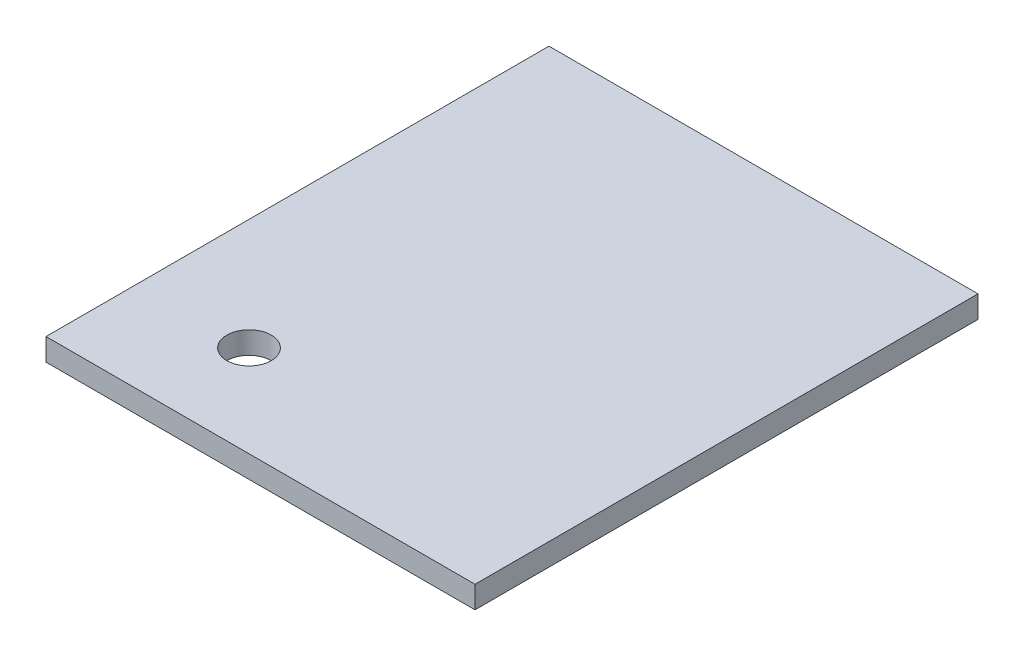
SolidWorks part; units mm, degrees
ref_plane "Front Plane" through (0, 0, 0) normal (0, 0, 1) x (1, 0, 0)
ref_plane "Top Plane" through (0, 0, 0) normal (0, 1, 0) x (1, 0, 0)
ref_plane "Right Plane" through (0, 0, 0) normal (1, 0, 0) x (0, 0, -1)
sketch "Sketch1" plane through (0, 0, 0) normal (0, 1, 0) x (1, 0, 0)
  line L1 (-26.3686, 11.4411) -> (31.6314, 11.4411)
  line L2 (-26.3686, 11.4411) -> (-26.3686, -56.5589)
  line L3 (-26.3686, -56.5589) -> (31.6314, -56.5589)
  line L4 (31.6314, 11.4411) -> (31.6314, -56.5589)
  dimension "D1" = 58
  dimension "D2" = 68
extrude "Boss-Extrude1" add sketch "Sketch1" along normal blind 3
hole_wizard "Ø8.0mm Dowel Hole1" positions "Sketch2" profile "Sketch3" hole size "Ø6.0" standard "ANSI Metric" end condition up to next
sketch "Sketch2" plane through (0, 0, 0) normal (0, -1, 0) x (-1, 0, 0)
  point P0 (11.3197, -44.16)
sketch "Sketch3" plane through (-11.3197, 0, 44.16) normal (1, 0, 0) x (0, 0, -1)
  line L0 (0, 0) -> (0, 3)
  line L1 (0, 3) -> (3, 3)
  line L2 (3, 3) -> (3, 0)
  line L5 (3, 0) -> (0, 0)
  line L11 (0, -6.35) -> (0, 107.95) construction
  dimension "Thru Hole Dia." = 6
  dimension "Thru Hole Depth" = 3
